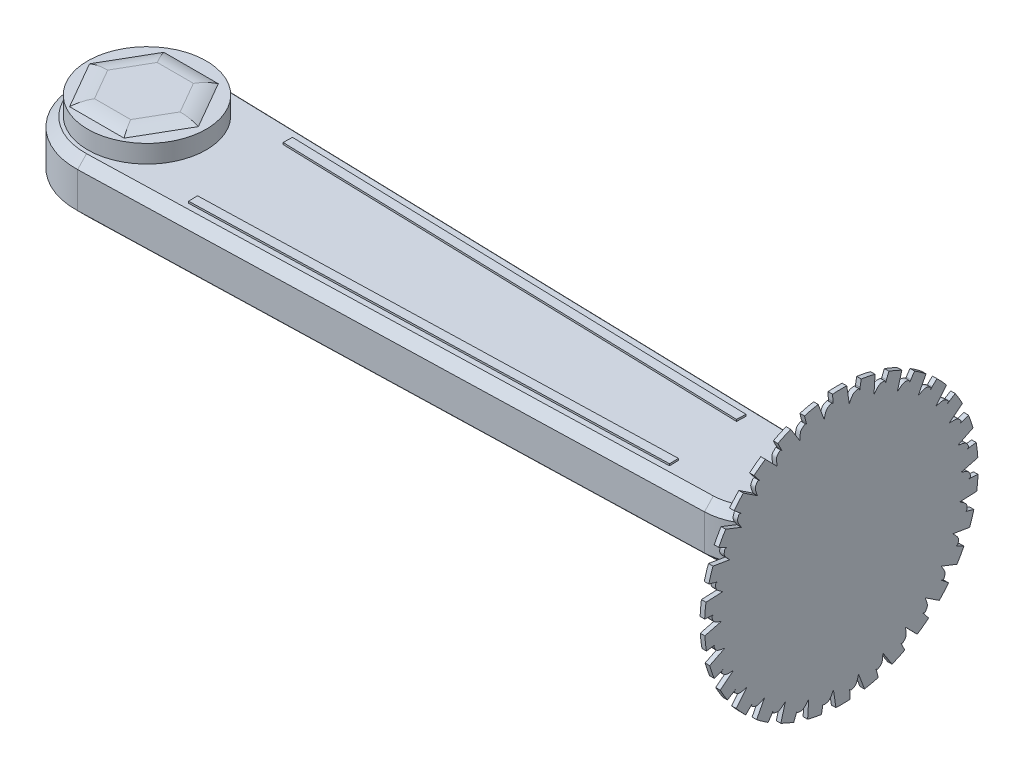
SolidWorks part; units mm, degrees
ref_plane "Front Plane" through (0, 0, 0) normal (0, 0, 1) x (1, 0, 0)
ref_plane "Top Plane" through (0, 0, 0) normal (0, 1, 0) x (1, 0, 0)
ref_plane "Right Plane" through (0, 0, 0) normal (1, 0, 0) x (0, 0, -1)
sketch "Sketch1" plane through (0, 0, 0) normal (0, 1, 0) x (1, 0, 0)
  line L0 (-75.1727, 19.3) -> (93.6924, 14.5493)
  line L1 (-75.1766, -20.6843) -> (94.6908, -15.9383)
  arc A0 (-75.1727, 19.3) -> (-75.1766, -20.6843) centre (-75.7352, -0.6921) ccw
  arc A1 (94.6908, -15.9383) -> (93.6924, 14.5493) centre (94.2648, -0.6921) ccw
  dimension "D1" = 170
extrude "Boss-Extrude2" add sketch "Sketch1" along normal mid plane 15 contours L0 A1 L1 A0
chamfer "Chamfer3" distance 2.54 angle 45 4 edges at (9.2598, 7.5, -16.9247) (109.5088, 7.5, 0.1929) (9.7571, 7.5, 18.3113) (-95.7352, 7.5, 0.6902)
chamfer "Chamfer4" distance 2.54 angle 45 4 edges at (9.7571, -7.5, 18.3113) (109.5088, -7.5, 0.1929) (9.2598, -7.5, -16.9247) (-95.7352, -7.5, 0.6902)
sketch "Sketch2" plane through (0, 7.5, 0) normal (0, 1, 0) x (1, 0, 0)
  circle A0 centre (-75.9727, -0.5801) radius 16.5
extrude "Boss-Extrude4" add sketch "Sketch2" along normal blind 5 contours A0
sketch "Sketch4" plane through (0, -7.5, 0) normal (0, -1, 0) x (1, 0, 0)
  circle A0 centre (-77.7643, 0) radius 5
extrude "Boss-Extrude5" add sketch "Sketch4" along normal blind 10
sketch "Sketch5" plane through (0, 12.5, 0) normal (0, 1, 0) x (1, 0, 0)
  line L1 (-83.9329, -14.1727) -> (-68.7749, -14.1727)
  line L2 (-68.7749, -14.1727) -> (-61.1958, -1.0455)
  line L3 (-61.1958, -1.0455) -> (-68.7749, 12.0818)
  line L4 (-68.7749, 12.0818) -> (-83.9329, 12.0818)
  line L5 (-83.9329, 12.0818) -> (-91.512, -1.0455)
  line L6 (-91.512, -1.0455) -> (-83.9329, -14.1727)
  circle A0 centre (-76.3539, -1.0455) radius 13.1273 construction
extrude "Boss-Extrude6" add sketch "Sketch5" along normal blind 1.016 contours L4 L5 L6 L1 L2 L3
sketch "Sketch6" plane through (0, 7.5, 0) normal (0, 1, 0) x (1, 0, 0)
  line L0 (-49.9938, 13.977) -> (79.9602, 10.321)
  line L1 (93.7082, 12.0079) -> (-75.2442, 16.761) construction
extrude "Extrude-Thin1" add sketch "Sketch6" along normal blind 0.508 thin contours L0
fillet "Fillet1" radius 10 6 edges at (-64.9854, 13.516, 7.6091) (-76.3539, 13.516, 14.1727) (-87.7225, 13.516, 7.6091) (-87.7225, 13.516, -5.5182) (-76.3539, 13.516, -12.0818) (-64.9854, 13.516, -5.5182)
sketch "Sketch7" plane through (0, 7.5, 0) normal (0, 1, 0) x (1, 0, 0)
  line L0 (-49.129, -13.356) -> (81.19, -9.7149)
  line L2 (-75.2475, -18.1453) -> (94.6199, -13.3993) construction
extrude "Extrude-Thin3" add sketch "Sketch7" along normal blind 0.508 thin contours L0
sketch "Sketch8" plane through (0, 7.5, 0) normal (0, 1, 0) x (1, 0, 0)
  line L1 (108.2373, 10.9709) -> (115.9206, 10.9709)
  line L2 (108.2373, 10.9709) -> (108.2373, -11.0546)
  line L3 (108.2373, -11.0546) -> (115.9206, -11.0546)
  line L4 (115.9206, 10.9709) -> (115.9206, -11.0546)
  line L5 (108.2373, 10.9709) -> (115.9206, -11.0546) construction
  line L6 (108.2373, -11.0546) -> (115.9206, 10.9709) construction
  point P0 (112.0789, -0.0418)
extrude "Cut-Extrude1" cut sketch "Sketch8" against normal blind 17.272 and the other way blind 10.16
sketch "Sketch9" plane through (108.2373, 0, 0) normal (1, 0, 0) x (0, 0, -1)
  line L1 (-1.69, 1.3093) -> (0.5874, 1.3093)
  line L2 (-1.69, 1.3093) -> (-1.69, -1.0556)
  line L3 (-1.69, -1.0556) -> (0.5874, -1.0556)
  line L4 (0.5874, 1.3093) -> (0.5874, -1.0556)
  line L5 (-1.69, 1.3093) -> (0.5874, -1.0556) construction
  line L6 (-1.69, -1.0556) -> (0.5874, 1.3093) construction
  point P0 (-0.5513, 0.1269)
extrude "Boss-Extrude7" add sketch "Sketch9" along normal blind 7.874
sketch "Sketch10" plane through (116.1113, 0, 0) normal (1, 0, 0) x (0, 0, -1)
  circle A0 centre (-0.5169, 0.1759) radius 38.1
extrude "Boss-Extrude8" add sketch "Sketch10" along normal blind 1.27
sketch "Sketch12" plane through (117.3813, 0, 0) normal (1, 0, 0) x (0, 0, -1)
  spline S0 degree 2 poles (-8.1675, 41.3263) (-6.8843, 37.2898) (-5.3093, 33.3106) knots 0 0 0 1 1 1
  spline S1 degree 3 poles (-5.3093, 33.3106) (-4.704, 35.752) (-4.264, 35.6484) (-2.9559, 36.2849) (-2.8126, 35.5783) knots 0 0 0 0 0.746376 1 1 1 1
  spline S2 degree 1 poles (-2.8126, 35.5783) (-2.8733, 36.3347) knots 0 0 1 1
  spline S3 degree 1 poles (-2.8733, 36.3347) (-3.0827, 42.6162) knots 0 0 1 1
  spline S4 degree 1 poles (-8.1675, 41.3263) (-3.0827, 42.6162) knots 0 0 1 1
  point P2 (-3.3058, 36.0447)
  point P6 (-5.2897, 33.0414)
  point P7 (-0.8089, 40.956)
  point P9 (-2.4002, 41.7098)
  point P10 (-2.1908, 35.4283)
  point P11 (-5.3316, 33.2508)
extrude "Cut-Extrude2" cut sketch "Sketch12" against normal blind 6.096
pattern_circular "CirPattern2" count 30 over 360 about axis through (117.3813, 0.1759, 0.5169) along (1, 0, 0) of "Cut-Extrude2"
